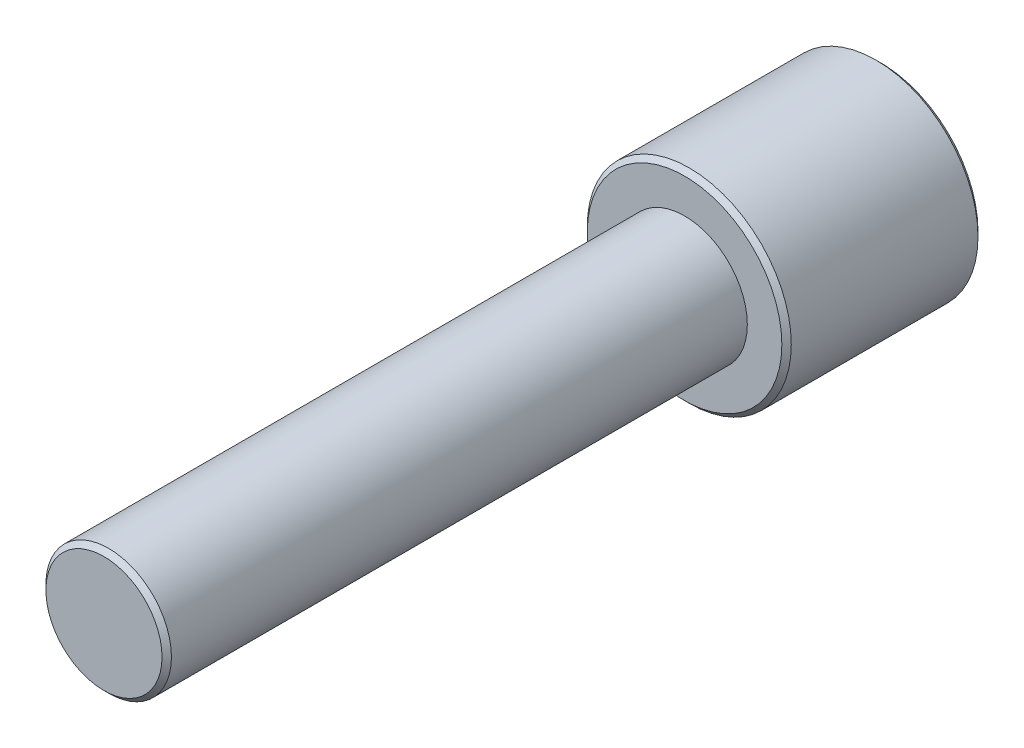
SolidWorks part; units mm, degrees
ref_plane "Спереди" through (0, 0, 0) normal (0, 0, 1) x (1, 0, 0)
ref_plane "Сверху" through (0, 0, 0) normal (0, 1, 0) x (1, 0, 0)
ref_plane "Справа" through (0, 0, 0) normal (1, 0, 0) x (0, 0, -1)
other "Configuration Table"
sketch "Эскиз1" plane through (0, 0, 0) normal (0, 0, 1) x (1, 0, 0)
  circle A0 centre (0, 0) radius 4
  point P2 (0, 0)
  point P3 (0, 0)
  point P4 (0, 0)
  point P6 (0, 0)
  point P7 (0, 0)
  dimension "D1" = 8
extrude "Бобышка-Вытянуть2" add sketch "Эскиз1" along normal blind 37 contours A0
sketch "Эскиз4" plane through (0, 0, 0) normal (0, 0, -1) x (-1, 0, 0)
  circle A0 centre (0, 0) radius 6.5
  point P3 (0, 0)
  dimension "D1" = 13
extrude "Бобышка-Вытянуть3" add sketch "Эскиз4" along normal blind 12.5
sketch "Эскиз5" plane through (0, 0, -12.5) normal (0, 0, -1) x (-1, 0, 0)
  circle A0 centre (0, 0) radius 2.75
  dimension "D1" = 5.5
extrude "Вырез-Вытянуть1" cut sketch "Эскиз5" against normal blind 12.5
sketch "Эскиз6" plane through (0, 0, -12.5) normal (0, 0, -1) x (-1, 0, 0)
  circle A0 centre (0, 0) radius 2.5
  dimension "D1" = 5
extrude "Вырез-Вытянуть2" cut sketch "Эскиз6" against normal blind 26.5
chamfer "Фаска1" distance 0.3 1 edges at (-6.5, 0, -12.5)
chamfer "Фаска2" distance 0.3 angle 45 2 edges at (-6.5, 0, 0) (4, 0, 37)
thread "Резьба1" pitch 0.8 method extrude profile "Профиль резьбы1" start angle 0, offset 0, length 10, pitch 0.8, diameter 5
ref_plane "Плоскость1" through (2.5, 0, 0) normal (0, -1, 0) x (1, 0, 0)
sketch "Профиль резьбы1" plane through (2.5, 0, 0) normal (0, -1, 0) x (1, 0, 0)
  line L0 (0, 0) -> (0, 0.8) construction
  line L11 (0, 0) -> (0, 0.7)
  line L12 (0, 0.7) -> (-0.433, 0.45)
  line L13 (-0.433, 0.45) -> (-0.433, 0.25)
  line L15 (-0.433, 0.25) -> (0, 0)
  line L17 (-0.433, 0.35) -> (0, 0.35) construction
  point P2 (0, 0)
  dimension "Pitch" = 0.8
  dimension "Profile_Angle" = 60
  dimension "Profile_Land" = 0.2
  dimension "Profile_Height" = 0.433
